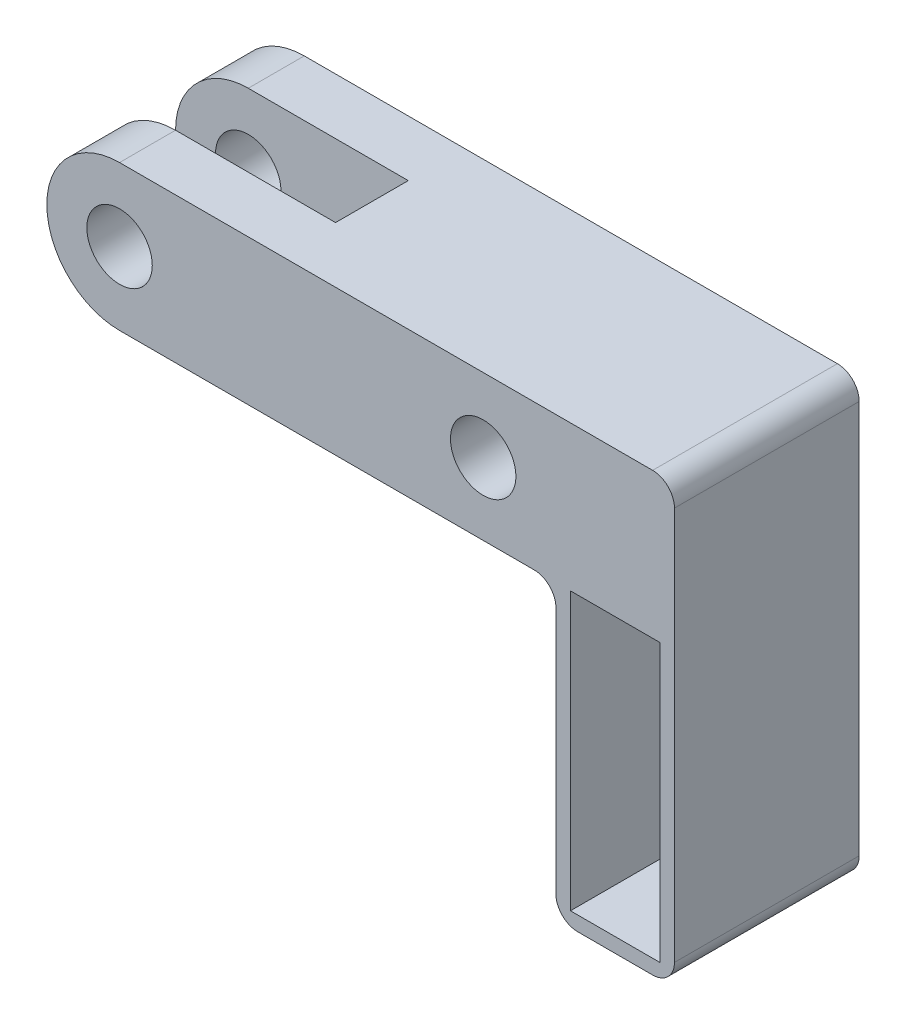
SolidWorks part; units mm, degrees
ref_plane "Front Plane" through (0, 0, 0) normal (0, 0, 1) x (1, 0, 0)
ref_plane "Top Plane" through (0, 0, 0) normal (0, 1, 0) x (1, 0, 0)
ref_plane "Right Plane" through (0, 0, 0) normal (1, 0, 0) x (0, 0, -1)
sketch "Sketch1" plane through (0, 0, 0) normal (0, 0, 1) x (1, 0, 0)
  line L0 (0, -5) -> (30, -5)
  line L1 (0, 5) -> (38.15, 5)
  line L10 (38.15, 5) -> (38.15, -25.05)
  line L11 (38.15, -25.05) -> (30, -25.05)
  line L12 (30, -5) -> (30, -25.05)
  line L14 (31, -24.05) -> (37.15, -24.05)
  line L15 (31, -24.05) -> (31, -5)
  line L16 (31, -5) -> (37.15, -5)
  line L17 (37.15, -24.05) -> (37.15, -5)
  arc A0 (0, 5) -> (0, -5) centre (0, 0) ccw
  circle A2 centre (0, 0) radius 2.25
  circle A4 centre (25, -0.0668) radius 2.25
  dimension "D1" = 5
  dimension "D3" = 4.5
  dimension "D11" = 4.5
  dimension "D2" = 30
  dimension "D4" = 1
  dimension "D5" = 1
  dimension "D6" = 1
  dimension "D7" = 6.15
  dimension "D8" = 19.05
  dimension "D9" = 10
  dimension "D10" = 6
extrude "Boss-Extrude1" add sketch "Sketch1" along normal mid plane 12.7 contours L1 A0 A2 region at (19.237, -1.7289, 0)
sketch "Sketch13" plane through (0, -5, 0) normal (0, -1, 0) x (1, 0, 0)
  line L0 (-5, 6.35) -> (-5, -6.35) construction
  line L1 (-5, -2.5) -> (11, -2.5)
  line L2 (-5, -2.5) -> (-5, 2.5)
  line L3 (-5, 2.5) -> (11, 2.5)
  line L4 (11, -2.5) -> (11, 2.5)
  point P6 (-5, 0)
  dimension "D1" = 5
  dimension "D2" = 16
extrude "Cut-Extrude1" cut sketch "Sketch13" against normal blind 10
chamfer "Chamfer1" distance 8 distance2 10 1 edges at (11, -5, 0) tangent propagation no first distance on face at (10.25, -5, 0)
fillet "Fillet1" radius 1.5 4 edges at (30, -5, 0) (38.15, 5, 0) (38.15, -25.05, 0) (30, -25.05, 0)
